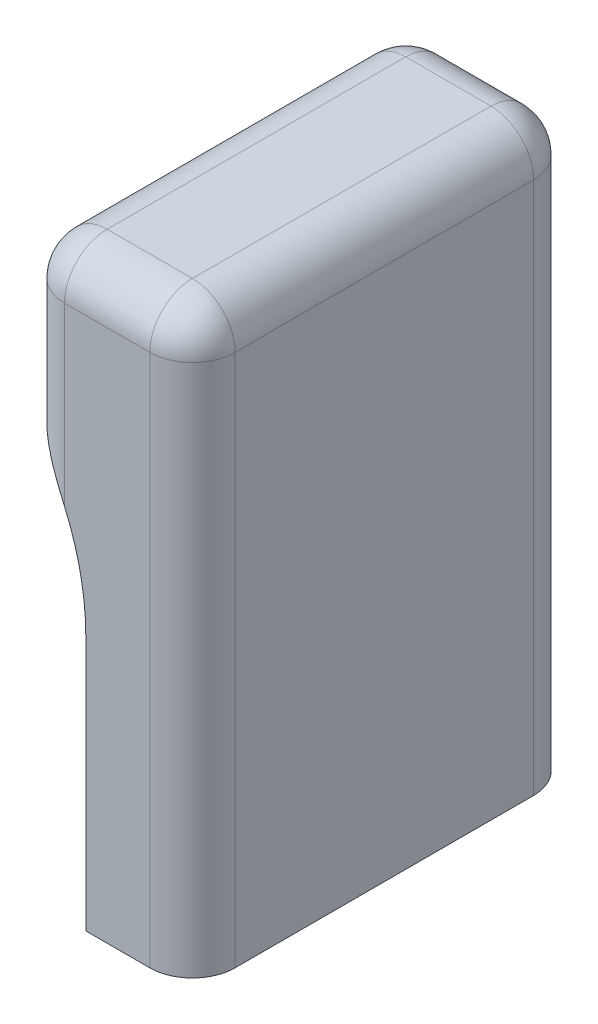
SolidWorks part; units mm, degrees
material "Silicon Rubber"
ref_plane "Front Plane" through (0, 0, 0) normal (0, 0, 1) x (1, 0, 0)
ref_plane "Top Plane" through (0, 0, 0) normal (0, 1, 0) x (1, 0, 0)
ref_plane "Right Plane" through (0, 0, 0) normal (1, 0, 0) x (0, 0, -1)
sketch "Sketch1" plane through (0, 0, 0) normal (0, 1, 0) x (1, 0, 0)
  line L1 (-4, -9) -> (4, -9)
  line L2 (-4, -9) -> (-4, 9)
  line L3 (-4, 9) -> (4, 9)
  line L4 (4, -9) -> (4, 9)
  line L5 (-4, -9) -> (4, 9) construction
  line L6 (-4, 9) -> (4, -9) construction
  point P0 (0, 0)
  dimension "D1" = 18
  dimension "D2" = 8
extrude "Boss-Extrude1" add sketch "Sketch1" along normal blind 27
sketch "Sketch2" plane through (0, 0, 9) normal (0, 0, 1) x (1, 0, 0)
  line L0 (55, 0) -> (-55, 0) construction
  line L1 (4, 27) -> (4, 0) construction
  circle A0 centre (-12.96, 11.96) radius 11.96
  dimension "D1" = 23.92
  dimension "D2" = 11.96
  dimension "D3" = 16.96
extrude "Cut-Extrude1" cut sketch "Sketch2" against normal blind 30
sketch "Sketch3" plane through (0, 0, 9) normal (0, 0, 1) x (1, 0, 0)
  line L0 (-1, 0) -> (-4.758, 0)
  line L1 (55, 0) -> (-55, 0) construction
  line L2 (-4.758, 0) -> (-4.758, 11.96)
  line L3 (-4.758, 11.96) -> (-1, 11.96)
  line L4 (-1, 11.96) -> (-1, 0)
  arc A0 (-4, 4.0379) -> (-4, 19.8821) centre (-12.96, 11.96) ccw construction
  point P5 (0, 0)
  point P11 (0, 0)
  point P12 (-4.7114, 12.4846)
  point P13 (0, 0)
  point P14 (-4.758, 11.96)
  point P15 (0, 0)
extrude "Cut-Extrude2" cut sketch "Sketch3" against normal blind 30
fillet "Fillet1" radius 2 1 edges at (4, 13.5, 9)
fillet "Fillet2" radius 2 6 edges at (-1, 27, 9) (3.4142, 27, 8.4142) (-4, 27, 0) (0, 27, -9) (4, 13.5, -9) (4, 27, -1)
fillet "Fillet3" radius 2 5 edges at (-3.4142, 26.4142, -8.4142) (-3.4142, 26.4142, 8.4142) (-4, 22.4411, -9) (-4, 22.4411, 9) (-4, 19.8821, 0)
